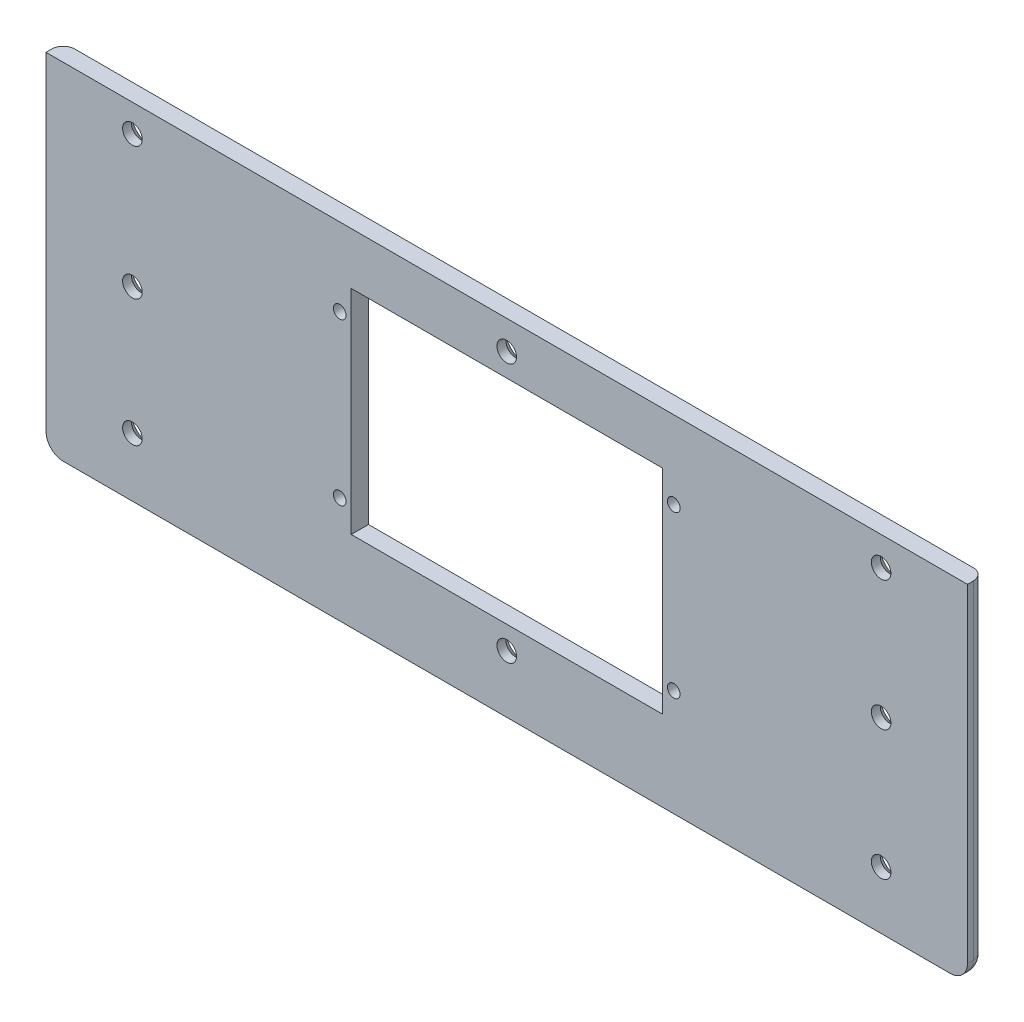
SolidWorks part; units mm, degrees
ref_plane "Front Plane" through (0, 0, 0) normal (0, 0, 1) x (1, 0, 0)
ref_plane "Top Plane" through (0, 0, 0) normal (0, 1, 0) x (1, 0, 0)
ref_plane "Right Plane" through (0, 0, 0) normal (1, 0, 0) x (0, 0, -1)
sketch "Sketch1" plane through (0, 0, 0) normal (0, 0, 1) x (1, 0, 0)
  line L1 (0, 0) -> (160, 0)
  line L2 (0, 0) -> (0, 60)
  line L3 (0, 60) -> (160, 60)
  line L4 (160, 0) -> (160, 60)
  dimension "D1" = 160
  dimension "D2" = 60
extrude "Boss-Extrude1" add sketch "Sketch1" along normal blind 3
sketch "Sketch2" plane through (0, 0, 0) normal (0, 0, -1) x (-1, 0, 0)
  line L0 (-53.5, 14.5) -> (-53.5, 50.5) construction
  line L1 (-106.5, 14.5) -> (-53.5, 14.5) construction
  line L2 (-106.5, 50.5) -> (-106.5, 14.5) construction
  line L3 (-53.5, 50.5) -> (-106.5, 50.5) construction
  line L4 (-53.5, 14.5) -> (-53.5, 50.5) construction
  line L5 (-106.5, 14.5) -> (-53.5, 14.5) construction
  line L6 (-106.5, 50.5) -> (-106.5, 14.5) construction
  line L7 (-53.5, 50.5) -> (-106.5, 50.5) construction
  line L9 (-107, 51) -> (-53, 51)
  line L10 (-107, 51) -> (-107, 14)
  line L11 (-107, 14) -> (-53, 14)
  line L12 (-53, 51) -> (-53, 14)
  circle A0 centre (-51, 18.5) radius 1.15 construction
  circle A1 centre (-51, 46.5) radius 1.15 construction
  circle A2 centre (-109, 18.5) radius 1.15 construction
  circle A3 centre (-109, 46.5) radius 1.15 construction
  circle A4 centre (-51, 18.5) radius 1.15 construction
  circle A5 centre (-51, 46.5) radius 1.15 construction
  circle A6 centre (-109, 18.5) radius 1.15 construction
  circle A7 centre (-109, 46.5) radius 1.15 construction
  circle A8 centre (-109, 46.5) radius 1.1
  circle A9 centre (-109, 18.5) radius 1.1
  circle A10 centre (-51, 18.5) radius 1.1
  circle A11 centre (-51, 46.5) radius 1.1
  dimension "D5" = 2.2
  dimension "D1" = 0.5
  dimension "D2" = 0.5
  dimension "D3" = 0.5
  dimension "D4" = 0.5
extrude "Cut-Extrude1" cut sketch "Sketch2" against normal through all
fillet "Fillet1" radius 2 3 edges at (80, 0, 0) (0, 30, 0) (160, 30, 0)
fillet "Fillet2" radius 3 4 edges at (159.4142, 0.5858, 0.5858) (0.5858, 0.5858, 0.5858) (0, 0, 2.5) (160, 0, 2.5)
sketch "Sketch4" plane through (0, 0, 0) normal (0, 0, -1) x (-1, 0, 0)
  line L0 (-80, 60) -> (-80, 55) construction
  line L1 (-158, 60) -> (-2, 60) construction
  line L2 (-80, 55) -> (-145, 55) construction
  line L3 (-145, 10) -> (-80, 10) construction
  line L4 (-80, 10) -> (-80, 55) construction
  circle A0 centre (-15, 55.2287) radius 3 construction
  circle A1 centre (-15, 32.2713) radius 3 construction
  circle A2 centre (-15, 10.2287) radius 3 construction
  circle A3 centre (-145, 10) radius 3 construction
  circle A4 centre (-145, 32.5) radius 3 construction
  circle A5 centre (-145, 55) radius 3 construction
  circle A6 centre (-15, 55.2287) radius 3
  circle A7 centre (-15, 32.2713) radius 3
  circle A8 centre (-15, 10.2287) radius 3
  circle A9 centre (-145, 10) radius 3
  circle A10 centre (-145, 32.5) radius 3
  circle A11 centre (-145, 55) radius 3
  circle A12 centre (-80, 55) radius 3
  circle A13 centre (-80, 10) radius 3
hole_wizard "CSK for M3 Flat Head Machine Screw1" positions "3DSketch1" profile "Sketch5" countersink size "M3" standard "ANSI Metric" end condition through all
sketch3d "3DSketch1"
  point P0 (145, 55, 0)
  point P3 (145, 32.5, 0)
  point P6 (145, 10, 0)
  point P9 (80, 10, 0)
  point P12 (80, 55, 0)
  point P15 (15, 55.2287, 0)
  point P18 (15, 32.2713, 0)
  point P21 (15, 10.2287, 0)
sketch "Sketch5" plane through (145, 55, 0) normal (1, 0, 0) x (0, 1, 0)
  line L0 (0, 0) -> (0, 3)
  line L1 (0, 3) -> (1.7, 3)
  line L2 (1.7, 3) -> (1.7, 1.45)
  line L3 (1.7, 1.45) -> (3.15, 0)
  line L5 (3.15, 0) -> (0, 0)
  line L6 (-1.7, 1.45) -> (-3.15, 0) construction
  line L11 (0, -6.35) -> (0, 107.95) construction
  dimension "Thru Hole Dia." = 3.4
  dimension "Thru Hole Depth" = 3
  dimension "Near C'Sink Dia." = 6.3
  dimension "Near C'Sink Angle" = 90
